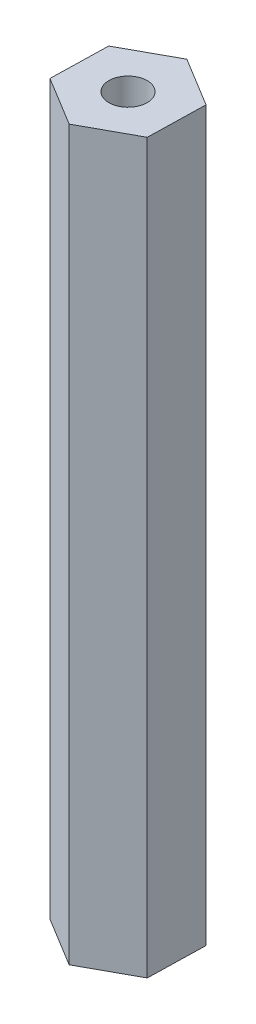
SolidWorks part; units mm, degrees
material "AISI 316 Annealed Stainless Steel Bar (SS)"
ref_plane "Front Plane" through (0, 0, 0) normal (0, 0, 1) x (1, 0, 0)
ref_plane "Top Plane" through (0, 0, 0) normal (0, 1, 0) x (1, 0, 0)
ref_plane "Right Plane" through (0, 0, 0) normal (1, 0, 0) x (0, 0, -1)
sketch "Sketch1" plane through (0, 0, 0) normal (0, 1, 0) x (1, 0, 0)
  line L1 (6.5846, 3.6022) -> (0.1727, 7.5036)
  line L2 (0.1727, 7.5036) -> (-6.4119, 3.9014)
  line L3 (-6.4119, 3.9014) -> (-6.5846, -3.6022)
  line L4 (-6.5846, -3.6022) -> (-0.1727, -7.5036)
  line L5 (-0.1727, -7.5036) -> (6.4119, -3.9014)
  line L6 (6.4119, -3.9014) -> (6.5846, 3.6022)
  circle A0 centre (0, 0) radius 6.5 construction
  circle A1 centre (0, 0) radius 2.5
  dimension "D2" = 5
  dimension "D1" = 13
extrude "Boss-Extrude1" add sketch "Sketch1" along normal mid plane 95 contours L1 L2 L3 L4 L5 L6
extrude "Cut-Extrude1" cut sketch "Sketch1<3>" against normal mid plane 104 contours A1 region at (0, 0, 0)
sketch "Sketch1<3>" plane through (0, 0, 0) normal (0, 1, 0) x (1, 0, 0) same geometry as "Sketch1"
cosmetic thread "Cosmetic Thread1" parameters "D1"=15, "D2"=6
